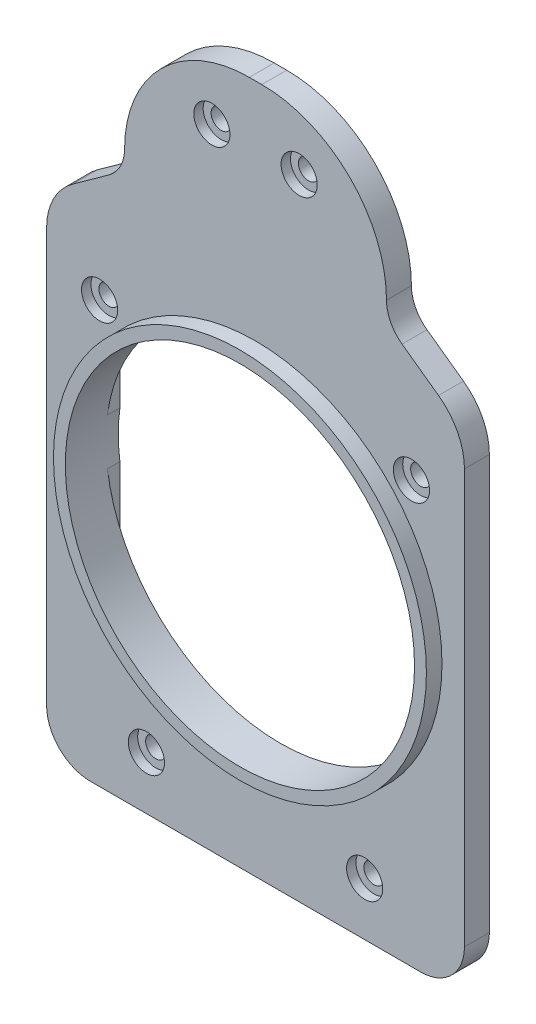
SolidWorks part; units mm, degrees
ref_plane "Plano frontal" through (0, 0, 0) normal (0, 0, 1) x (1, 0, 0)
ref_plane "Plano superior" through (0, 0, 0) normal (0, 1, 0) x (1, 0, 0)
ref_plane "Plano direito" through (0, 0, 0) normal (1, 0, 0) x (0, 0, -1)
sketch "Esboço1" plane through (0, 0, 0) normal (0, 0, 1) x (1, 0, 0)
  line L0 (-33.5, 0) -> (33.5, 0) construction
  line L1 (-33.5, -44.5) -> (33.5, -44.5)
  line L2 (-33.5, -44.5) -> (-33.5, 66)
  line L3 (-33.5, 66) -> (33.5, 66)
  line L4 (33.5, -44.5) -> (33.5, 66)
  point P0 (0, 0)
  point P8 (0, 0)
  dimension "D1" = 67
  dimension "D2" = 66
  dimension "D3" = 44.5
  dimension "D4" = 0
extrude "Ressalto-extrusão1" add sketch "Esboço1" along normal blind 4
sketch "Esboço12" plane through (0, 0, 4) normal (0, 0, 1) x (1, 0, 0)
  line L0 (0, 66) -> (0, -44.5) construction
  line L1 (-33.5, 66) -> (-21, 66)
  line L2 (-33.5, 66) -> (-33.5, 34)
  line L4 (-21, 66) -> (-21, 43)
  line L5 (33.5, 66) -> (-33.5, 66) construction
  line L6 (-33.5, -44.5) -> (33.5, -44.5) construction
  line L9 (33.5, 66) -> (33.5, 34)
  line L10 (33.5, 66) -> (21, 66)
  line L11 (-33.5, 34) -> (-21, 43)
  line L12 (33.5, 34) -> (21, 43)
  line L13 (21, 66) -> (21, 43)
  dimension "D1" = 32
  dimension "D2" = 23
  dimension "D3" = 12.5
extrude "Corte-extrusão4" cut sketch "Esboço12" against normal through all
fillet "Filete5" radius 7 2 edges at (33.5, -44.5, 2) (-33.5, -44.5, 2)
fillet "Filete6" radius 10 2 edges at (33.5, 34, 2) (-33.5, 34, 2)
fillet "Filete7" radius 6 2 edges at (-21, 43, 2) (21, 43, 2)
fillet "Filete8" radius 20 2 edges at (21, 66, 2) (-21, 66, 2)
sketch "Esboço13" plane through (0, 0, 0) normal (0, 0, -1) x (-1, 0, 0)
  line L6 (1.0001, 60.25) -> (-1.0001, 60.25)
  line L7 (25.9833, 32.3267) -> (20.1344, 36.5379)
  line L8 (27.75, -37.5) -> (27.75, 28.8777)
  line L9 (-26.5, -38.75) -> (26.5, -38.75)
  line L10 (-27.75, 28.8777) -> (-27.75, -37.5)
  line L11 (-20.1344, 36.5379) -> (-25.9833, 32.3267)
  line L12 (1.0001, 61.75) -> (-1.0001, 61.75)
  line L13 (-21.0109, 37.7552) -> (-26.8598, 33.544)
  line L14 (-29.25, 28.8777) -> (-29.25, -37.5)
  line L15 (-26.5, -40.25) -> (26.5, -40.25)
  line L16 (29.25, -37.5) -> (29.25, 28.8777)
  line L17 (26.8598, 33.544) -> (21.0109, 37.7552)
  line L18 (1.0001, 61.75) -> (-1.0001, 61.75)
  line L19 (-21.0109, 37.7552) -> (-26.8598, 33.544)
  line L20 (-29.25, 28.8777) -> (-29.25, -37.5)
  line L21 (-26.5, -40.25) -> (26.5, -40.25)
  line L22 (29.25, -37.5) -> (29.25, 28.8777)
  line L23 (26.8598, 33.544) -> (21.0109, 37.7552)
  arc A8 (-20.1344, 36.5379) -> (-15.25, 46.0402) centre (-27, 46.0734) ccw
  arc A9 (-1.0001, 60.25) -> (-15.25, 46.0402) centre (-1.0001, 46) ccw
  arc A10 (15.25, 46.0402) -> (1.0001, 60.25) centre (1.0001, 46) ccw
  arc A11 (15.25, 46.0402) -> (20.1344, 36.5379) centre (27, 46.0734) ccw
  arc A12 (27.75, 28.8777) -> (25.9833, 32.3267) centre (23.5, 28.8777) ccw
  arc A13 (26.5, -38.75) -> (27.75, -37.5) centre (26.5, -37.5) ccw
  arc A14 (-27.75, -37.5) -> (-26.5, -38.75) centre (-26.5, -37.5) ccw
  arc A15 (-25.9833, 32.3267) -> (-27.75, 28.8777) centre (-23.5, 28.8777) ccw
  arc A16 (-1.0001, 61.75) -> (-16.75, 46.0445) centre (-1.0001, 46) ccw
  arc A17 (-21.0109, 37.7552) -> (-16.75, 46.0445) centre (-27, 46.0734) ccw
  arc A18 (-26.8598, 33.544) -> (-29.25, 28.8777) centre (-23.5, 28.8777) ccw
  arc A19 (-29.25, -37.5) -> (-26.5, -40.25) centre (-26.5, -37.5) ccw
  arc A20 (26.5, -40.25) -> (29.25, -37.5) centre (26.5, -37.5) ccw
  arc A21 (29.25, 28.8777) -> (26.8598, 33.544) centre (23.5, 28.8777) ccw
  arc A22 (16.75, 46.0445) -> (21.0109, 37.7552) centre (27, 46.0734) ccw
  arc A23 (16.75, 46.0445) -> (1.0001, 61.75) centre (1.0001, 46) ccw
  arc A24 (-1.0001, 61.75) -> (-16.75, 46.0445) centre (-1.0001, 46) ccw
  arc A25 (-21.0109, 37.7552) -> (-16.75, 46.0445) centre (-27, 46.0734) ccw
  arc A26 (-26.8598, 33.544) -> (-29.25, 28.8777) centre (-23.5, 28.8777) ccw
  arc A27 (-29.25, -37.5) -> (-26.5, -40.25) centre (-26.5, -37.5) ccw
  arc A28 (26.5, -40.25) -> (29.25, -37.5) centre (26.5, -37.5) ccw
  arc A29 (29.25, 28.8777) -> (26.8598, 33.544) centre (23.5, 28.8777) ccw
  arc A30 (16.75, 46.0445) -> (21.0109, 37.7552) centre (27, 46.0734) ccw
  arc A31 (16.75, 46.0445) -> (1.0001, 61.75) centre (1.0001, 46) ccw
  dimension "D1" = 4.25
  dimension "D2" = 1.5
extrude "Ressalto-extrusão2" add sketch "Esboço13" along normal blind 2
sketch "Esboço14" plane through (0, 0, 4) normal (0, 0, 1) x (1, 0, 0)
  line L0 (0, 0) -> (0, -44.5) construction
  line L1 (-26.5, -44.5) -> (26.5, -44.5) construction
  circle A0 centre (-7, 56.5) radius 1.625
  circle A1 centre (-25, 23.08) radius 1.625
  circle A2 centre (-17.5, -36) radius 1.625
  circle A3 centre (17.5, -36) radius 1.625
  circle A4 centre (25, 23.08) radius 1.625
  circle A5 centre (7, 56.5) radius 1.625
  dimension "D1" = 7
  dimension "D2" = 56.5
  dimension "D3" = 25
  dimension "D4" = 23.08
  dimension "D5" = 36
  dimension "D6" = 17.5
  dimension "D7" = 3.25
  dimension "D8" = 3.25
  dimension "D9" = 3.25
extrude "Corte-extrusão5" cut sketch "Esboço14" against normal through all
sketch "Esboço15" plane through (0, 0, 4) normal (0, 0, 1) x (1, 0, 0)
  line L0 (0, -44.5) -> (0, 0) construction
  line L1 (-26.5, -44.5) -> (26.5, -44.5) construction
  circle A0 centre (-7, 56.5) radius 2.9
  circle A1 centre (-25, 23.08) radius 2.9
  circle A2 centre (-17.5, -36) radius 2.9
  circle A3 centre (17.5, -36) radius 2.9
  circle A4 centre (25, 23.08) radius 2.9
  circle A5 centre (7, 56.5) radius 2.9
  dimension "D1" = 5.8
  dimension "D2" = 5.8
  dimension "D3" = 5.8
extrude "Corte-extrusão6" cut sketch "Esboço15" against normal blind 1.5
sketch "Esboço16" plane through (0, 0, 0) normal (0, 0, -1) x (-1, 0, 0)
  line L0 (-33.5, -37.5) -> (-33.5, 28.8777) construction
  line L1 (-16.5, 19.08) -> (-33.5, 19.08)
  line L2 (-16.5, 19.08) -> (-16.5, 27.08)
  line L3 (-16.5, 27.08) -> (-33.5, 27.08)
  line L4 (-33.5, 19.08) -> (-33.5, 27.08)
  line L5 (-16.5, 19.08) -> (-33.5, 27.08) construction
  line L6 (-16.5, 27.08) -> (-33.5, 19.08) construction
  line L7 (26.5, -44.5) -> (-26.5, -44.5) construction
  line L8 (-21.5, -27.5) -> (-13.5, -27.5)
  line L9 (-21.5, -27.5) -> (-21.5, -44.5)
  line L10 (-21.5, -44.5) -> (-13.5, -44.5)
  line L11 (-13.5, -27.5) -> (-13.5, -44.5)
  line L12 (-21.5, -27.5) -> (-13.5, -44.5) construction
  line L13 (-21.5, -44.5) -> (-13.5, -27.5) construction
  line L14 (0, 0) -> (0, -44.5) construction
  line L15 (-3, 49.6794) -> (-11, 49.6794)
  line L16 (-3, 49.6794) -> (-3, 63.3206)
  line L17 (-3, 63.3206) -> (-11, 63.3206)
  line L18 (-11, 49.6794) -> (-11, 63.3206)
  line L19 (-3, 49.6794) -> (-11, 63.3206) construction
  line L20 (-3, 63.3206) -> (-11, 49.6794) construction
  line L21 (3, 63.3206) -> (11, 49.6794) construction
  line L22 (3, 49.6794) -> (11, 63.3206) construction
  line L23 (21.5, -44.5) -> (13.5, -27.5) construction
  line L24 (21.5, -27.5) -> (13.5, -44.5) construction
  line L25 (16.5, 27.08) -> (33.5, 19.08) construction
  line L26 (16.5, 19.08) -> (33.5, 27.08) construction
  line L27 (11, 49.6794) -> (11, 63.3206)
  line L28 (3, 63.3206) -> (11, 63.3206)
  line L29 (3, 49.6794) -> (3, 63.3206)
  line L30 (3, 49.6794) -> (11, 49.6794)
  line L31 (13.5, -27.5) -> (13.5, -44.5)
  line L32 (21.5, -44.5) -> (13.5, -44.5)
  line L33 (21.5, -27.5) -> (21.5, -44.5)
  line L34 (21.5, -27.5) -> (13.5, -27.5)
  line L35 (33.5, 19.08) -> (33.5, 27.08)
  line L36 (16.5, 27.08) -> (33.5, 27.08)
  line L37 (16.5, 19.08) -> (16.5, 27.08)
  line L38 (16.5, 19.08) -> (33.5, 19.08)
  arc A0 (-1.0001, 66) -> (-21, 46.0565) centre (-1.0001, 46) ccw construction
  point P0 (-25, 23.08)
  point P8 (-17.5, -36)
  point P16 (-7, 56.5)
  point P40 (7, 56.5)
  point P41 (17.5, -36)
  point P42 (25, 23.08)
  dimension "D1" = 8
  dimension "D2" = 8
  dimension "D3" = 8
extrude "Corte-extrusão7" cut sketch "Esboço16" along normal through all
sketch "Esboço18" plane through (0, 0, 4) normal (0, 0, 1) x (1, 0, 0)
  circle A0 centre (0, 0) radius 29.9
  circle A1 centre (0, 0) radius 28
  dimension "D1" = 59.8
  dimension "D2" = 56
extrude "Ressalto-extrusão3" add sketch "Esboço18" along normal blind 2.5
sketch "Esboço19" plane through (0, 0, 4) normal (0, 0, 1) x (1, 0, 0)
  circle A0 centre (0, 0) radius 28
extrude "Corte-extrusão8" cut sketch "Esboço19" against normal through all
sketch "Esboço20" plane through (0, 0, 0) normal (0, 0, -1) x (-1, 0, 0)
  line L6 (-1.0001, 66) -> (1.0001, 66) construction
  line L10 (-21, 21.4243) -> (-21, 31.0222)
  line L11 (-21, 31.0222) -> (-3.6374, 49.4307)
  line L12 (0, 51) -> (0, 0) construction
  line L13 (21, 31.0222) -> (3.6374, 49.4307)
  line L14 (21, 21.4243) -> (21, 31.0222)
  arc A4 (3.6374, 49.4307) -> (-3.6374, 49.4307) centre (0, 46) ccw
  arc A5 (21, 21.4243) -> (-21, 21.4243) centre (0, 0) ccw
  point P4 (0, 66)
  dimension "D1" = 20
  dimension "D2" = 10
  dimension "D3" = 60
  dimension "D4" = 21
extrude "Corte-extrusão9" cut sketch "Esboço20" against normal blind 3.5
fillet "Filete9" radius 0.5 4 edges at (21, 31.0222, 1.75) (-21, 31.0222, 1.75) (-21, 21.4243, 1.75) (21, 21.4243, 1.75)
